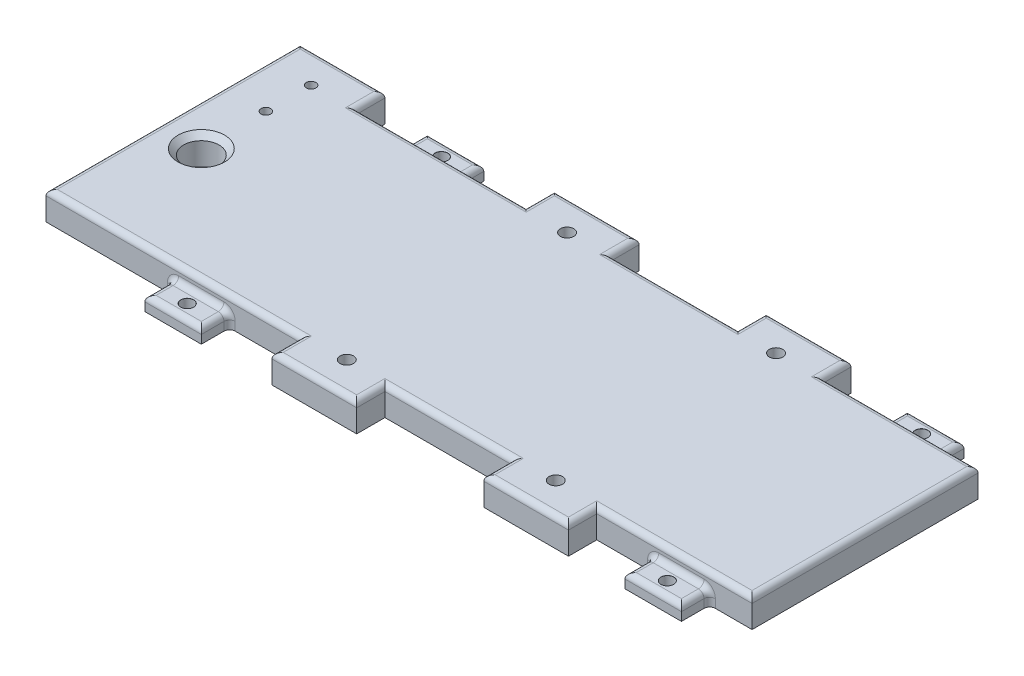
SolidWorks part; units mm, degrees
ref_plane "Front Plane" through (0, 0, 0) normal (0, 0, 1) x (1, 0, 0)
ref_plane "Top Plane" through (0, 0, 0) normal (0, 1, 0) x (1, 0, 0)
ref_plane "Right Plane" through (0, 0, 0) normal (1, 0, 0) x (0, 0, -1)
sketch "Sketch1" plane through (0, 0, 0) normal (0, 1, 0) x (1, 0, 0)
  line L1 (130, -50) -> (-130, -50)
  line L2 (130, -50) -> (130, 50)
  line L3 (130, 50) -> (-130, 50)
  line L4 (-130, -50) -> (-130, 50)
  line L5 (0, 50) -> (0, -50) construction
  line L6 (130, 0) -> (-130, 0) construction
  point P0 (0, 0)
  dimension "D1" = 260
  dimension "D2" = 100
extrude "Boss-Extrude1" add sketch "Sketch1" along normal blind 10
sketch "Sketch3" plane through (0, 10, 0) normal (0, 1, 0) x (1, 0, 0)
  line L0 (130, 50) -> (-130, 50) construction
  line L1 (130, 50) -> (75, 50)
  line L2 (130, 50) -> (130, 40)
  line L3 (130, 40) -> (75, 40)
  line L4 (75, 50) -> (75, 40)
  line L5 (130, -50) -> (75, -50)
  line L6 (130, -50) -> (130, -40)
  line L7 (130, -40) -> (75, -40)
  line L8 (75, -50) -> (75, -40)
  line L9 (-130, -50) -> (-30, -50)
  line L10 (-130, -50) -> (-130, -40)
  line L11 (-120, -40) -> (-30, -40)
  line L12 (-30, -50) -> (-30, -40)
  line L13 (-90, 50) -> (-30, 50)
  line L14 (-90, 50) -> (-90, 40)
  line L15 (-90, 40) -> (-30, 40)
  line L16 (-30, 50) -> (-30, 40)
  line L17 (-130, 50) -> (-130, -50) construction
  line L18 (-130, -50) -> (130, -50) construction
  line L19 (0, 50) -> (45, 50)
  line L20 (0, 50) -> (0, 40)
  line L21 (0, 40) -> (45, 40)
  line L22 (45, 50) -> (45, 40)
  line L23 (0, -50) -> (45, -50)
  line L24 (0, -50) -> (0, -40)
  line L25 (0, -40) -> (45, -40)
  line L26 (45, -50) -> (45, -40)
  line L28 (-130, 50) -> (-120, 50)
  line L29 (-130, 50) -> (-130, -40)
  line L31 (-120, 50) -> (-120, -40)
  dimension "D1" = 10
  dimension "D2" = 55
  dimension "D3" = 55
  dimension "D4" = 10
  dimension "D5" = 10
  dimension "D6" = 100
  dimension "D7" = 10
  dimension "D8" = 60
  dimension "D9" = 40
  dimension "D10" = 10
  dimension "D11" = 45
  dimension "D12" = 30
  dimension "D13" = 10
  dimension "D14" = 45
  dimension "D15" = 10
extrude "Cut-Extrude2" cut sketch "Sketch3" against normal through all
sketch "Sketch4" plane through (0, 10, 0) normal (0, 1, 0) x (1, 0, 0)
  circle A0 centre (59.5, 39) radius 2.375
  circle A1 centre (-14.5, 39) radius 2.375
  circle A2 centre (59.5, -39) radius 2.375
  circle A3 centre (-14.5, -39) radius 2.375
  dimension "D1" = 4.75
  dimension "D2" = 4.75
  dimension "D3" = 4.75
  dimension "D4" = 4.75
sketch "Sketch5" plane through (0, 0, 0) normal (0, -1, 0) x (1, 0, 0)
  line L0 (-30, 40) -> (-120, 40) construction
  line L1 (-75, 40) -> (-55, 40)
  line L2 (-75, 40) -> (-75, 50)
  line L3 (-75, 50) -> (-55, 50)
  line L4 (-55, 40) -> (-55, 50)
  line L5 (-90, -40) -> (-30, -40) construction
  line L6 (-75, -40) -> (-55, -40)
  line L7 (-75, -40) -> (-75, -50)
  line L8 (-75, -50) -> (-55, -50)
  line L9 (-55, -40) -> (-55, -50)
  line L10 (130, 40) -> (75, 40) construction
  line L11 (95, 40) -> (115, 40)
  line L12 (95, 40) -> (95, 50)
  line L13 (95, 50) -> (115, 50)
  line L14 (115, 40) -> (115, 50)
  line L15 (75, -40) -> (130, -40) construction
  line L16 (95, -40) -> (115, -40)
  line L17 (95, -40) -> (95, -50)
  line L18 (95, -50) -> (115, -50)
  line L19 (115, -40) -> (115, -50)
  line L20 (130, 40) -> (130, -40) construction
  dimension "D1" = 20
  dimension "D2" = 20
  dimension "D3" = 20
  dimension "D4" = 20
  dimension "D5" = 10
  dimension "D6" = 10
  dimension "D7" = 10
  dimension "D8" = 10
  dimension "D9" = 150
  dimension "D10" = 15
extrude "Boss-Extrude2" add sketch "Sketch5" against normal blind 5
fillet "Fillet1" radius 2 46 edges at (130, 10, 0) (-60, 10, -40) (-30, 10, -45) (-15, 10, -50) (60, 10, -50) (75, 10, -45) (102.5, 10, -40) (102.5, 10, 40) (75, 10, 45) (-30, 10, 45) (-75, 10, 40) (-90, 10, -45) (60, 10, 50) (45, 10, 45) (22.5, 10, 40) (0, 10, 45) (-15, 10, 50) (0, 10, -45) (22.5, 10, -40) (45, 10, -45) (-120, 10, -5) (-105, 10, -50) (-75, 2.5, 40) (-55, 2.5, 40) (95, 2.5, 40) (115, 2.5, 40) (115, 2.5, -40) (95, 2.5, -40) (-55, 2.5, -40) (-75, 2.5, -40) (-65, 5, 40) (-55, 5, 45) (-65, 5, 50) (-75, 5, 45) (105, 5, 40) (115, 5, 45) (105, 5, 50) (95, 5, 45) (105, 5, -50) (115, 5, -45) (105, 5, -40) (95, 5, -45) (-65, 5, -50) (-55, 5, -45) (-65, 5, -40) (-75, 5, -45)
sketch "Sketch2" plane through (0, 10, 0) normal (0, 1, 0) x (1, 0, 0)
  line L1 (-120, -40) -> (-120, 50) construction
  circle A0 centre (-105, 0) radius 6.25
  dimension "D2" = 12.5
  dimension "D1" = 15
extrude "Cut-Extrude1" cut sketch "Sketch2" against normal through all
chamfer "Chamfer1" distance 2 angle 45 1 edges at (-105, 10, 6.25)
extrude "Cut-Extrude3" cut sketch "Sketch4" against normal blind 6.2
sketch "Sketch9" plane through (0, 5, 0) normal (0, 1, 0) x (1, 0, 0)
  point P0 (-65, 45)
  point P2 (105, 45)
  point P4 (105, -45)
  point P6 (-65, -45)
hole_wizard "M4 Clearance Hole1" positions "Sketch9" profile "Sketch7" hole size "M4" standard "ANSI Metric" end condition through all
sketch "Sketch7" plane through (-65, 5, -45) normal (1, 0, 0) x (0, 0, 1)
  line L0 (0, 0) -> (0, 5)
  line L1 (0, 5) -> (2.25, 5)
  line L2 (2.25, 5) -> (2.25, 0.025)
  line L3 (2.25, 0.025) -> (2.275, 0)
  line L5 (2.275, 0) -> (0, 0)
  line L6 (-2.25, 0.025) -> (-2.275, 0) construction
  line L11 (0, -6.35) -> (0, 107.95) construction
  dimension "Thru Hole Dia." = 4.5
  dimension "Thru Hole Depth" = 5
  dimension "Near C'Sink Dia." = 4.55
  dimension "Near C'Sink Angle" = 90
sketch "Sketch12" plane through (0, 0, 0) normal (0, -1, 0) x (-1, 0, 0)
  line L1 (90, 50) -> (120, 50) construction
  line L2 (120, -40) -> (120, 50) construction
  point P0 (105, 38.8589)
  point P2 (105, 22.8589)
  point P11 (0, 0)
  dimension "D1" = 16
  dimension "D2" = 11.1411
  dimension "D3" = 15
hole_wizard "M3 Clearance Hole1" positions "Sketch12" profile "Sketch11" hole size "M3" standard "ANSI Metric" end condition through all
sketch "Sketch11" plane through (-105, 0, -38.8589) normal (1, 0, 0) x (0, 0, -1)
  line L0 (0, 0) -> (0, 10)
  line L1 (0, 10) -> (1.7, 10)
  line L2 (1.7, 10) -> (1.7, 0)
  line L5 (1.7, 0) -> (0, 0)
  line L11 (0, -6.35) -> (0, 107.95) construction
  dimension "Thru Hole Dia." = 3.4
  dimension "Thru Hole Depth" = 10
sketch "Sketch13" plane through (0, 0, 0) normal (0, -1, 0) x (1, 0, 0)
  circle A0 centre (-105, -22.8589) radius 3.5
  circle A1 centre (-105, -38.8589) radius 3.5
  dimension "D1" = 7
  dimension "D2" = 7
extrude "Cut-Extrude4" cut sketch "Sketch13" against normal blind 5
